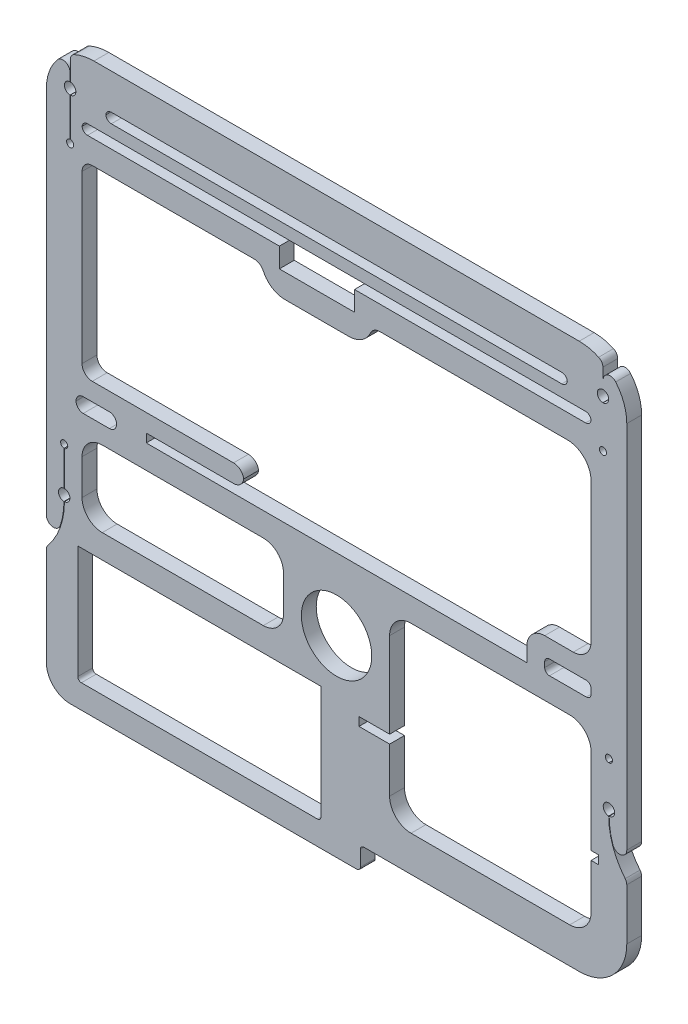
SolidWorks part; units mm, degrees
ref_plane "Front Plane" through (0, 0, 0) normal (0, 0, 1) x (1, 0, 0)
ref_plane "Top Plane" through (0, 0, 0) normal (0, 1, 0) x (1, 0, 0)
ref_plane "Right Plane" through (0, 0, 0) normal (1, 0, 0) x (0, 0, -1)
sketch "Sketch1" plane through (0, 0, 0) normal (0, 0, 1) x (1, 0, 0)
  line L0 (63.9883, 88.3985) -> (63.9883, 84.5885) construction
  line L1 (48.2422, 30.1083) -> (110.2188, 30.1083)
  line L2 (48.2422, 30.1083) -> (48.2422, 88.3985)
  line L3 (48.2422, 88.3985) -> (110.2188, 88.3985)
  line L4 (110.2188, 30.1083) -> (110.2188, 88.3985)
  line L5 (106.4088, 84.5885) -> (52.0522, 84.5885)
  line L6 (106.4088, 84.5885) -> (106.4088, 33.9183)
  line L7 (106.4088, 33.9183) -> (52.0522, 33.9183)
  line L8 (52.0522, 84.5885) -> (52.0522, 33.9183)
  line L9 (63.9883, 86.4935) -> (18.0707, 86.4935) construction
  line L10 (52.0522, 41.2855) -> (48.2422, 41.2855) construction
  line L11 (50.1472, 41.2855) -> (50.1472, 25.8577) construction
  line L12 (13.5248, 33.9183) -> (13.5248, 30.1083) construction
  line L13 (13.5248, 32.0133) -> (21.1598, 32.0133) construction
  line L14 (110.2188, 38.1916) -> (106.4088, 38.1916) construction
  line L15 (108.3138, 38.1916) -> (108.3138, 22.3321) construction
  line L16 (106.4088, 54.6152) -> (106.4088, 79.5085) construction
  line L17 (52.0522, 74.5555) -> (52.0522, 54.6152) construction
  line L22 (79.0876, 86.4935) -> (79.6338, 86.4935) construction
  line L23 (96.5564, 32.0133) -> (96.0102, 32.0133) construction
  dimension "D1" = 3.81
  dimension "D2" = 3.81
extrude "Boss-Extrude1" add sketch "Sketch1" along normal blind 1.5875
sketch "Sketch2" plane through (0, 0, 0) normal (0, 0, -1) x (-1, 0, 0)
  line L0 (-106.4088, 33.9183) -> (-106.4088, 84.5885) construction
  line L1 (-106.4088, 55.8724) -> (-52.0522, 55.8724)
  line L2 (-106.4088, 55.8724) -> (-106.4088, 53.3324)
  line L3 (-106.4088, 53.3324) -> (-52.0522, 53.3324)
  line L4 (-52.0522, 55.8724) -> (-52.0522, 53.3324)
  line L5 (-52.0522, 84.5885) -> (-52.0522, 33.9183) construction
  line L7 (-99.5505, 55.8724) -> (-58.9105, 55.8724) construction
  line L8 (-99.4108, 81.1849) -> (-61.0568, 81.1849) construction
  line L9 (-80.5132, 79.0767) -> (-73.7568, 79.0767) construction
  line L10 (-80.5132, 81.1849) -> (-80.5132, 79.0767) construction
  line L11 (-106.4088, 81.1849) -> (-81.1482, 81.1849)
  line L12 (-106.4088, 81.1849) -> (-106.4088, 78.6449)
  line L13 (-106.4088, 78.6449) -> (-83.0532, 78.6449)
  line L14 (-52.0522, 81.1849) -> (-52.0522, 78.6449)
  line L15 (-106.4088, 83.5217) -> (-52.0522, 83.5217)
  line L16 (-106.4088, 83.5217) -> (-106.4088, 82.2517)
  line L17 (-106.4088, 82.2517) -> (-52.0522, 82.2517)
  line L18 (-52.0522, 83.5217) -> (-52.0522, 82.2517)
  line L19 (-73.7568, 79.0767) -> (-73.7568, 81.1849) construction
  line L20 (-80.5132, 81.1849) -> (-80.5132, 79.0767) construction
  line L21 (-73.7568, 79.0767) -> (-73.7568, 81.1849) construction
  line L22 (-81.1482, 79.0767) -> (-81.1482, 81.1849)
  line L23 (-73.1218, 79.0767) -> (-81.1482, 79.0767)
  line L24 (-73.1218, 79.0767) -> (-73.1218, 81.1849)
  line L25 (-83.0532, 78.6449) -> (-83.0532, 76.5367)
  line L26 (-83.0532, 76.5367) -> (-71.2168, 76.5367)
  line L27 (-71.2168, 76.5367) -> (-71.2168, 78.6449)
  line L28 (-71.2168, 78.6449) -> (-52.0522, 78.6449)
  line L29 (-73.1218, 81.1849) -> (-52.0522, 81.1849)
  line L30 (-81.1482, 71.7401) -> (-80.5132, 71.7401) construction
  line L31 (-57.9086, 84.5885) -> (-57.9086, 83.5217) construction
  line L32 (-73.7568, 71.6584) -> (-73.1218, 71.6584) construction
  line L33 (-106.4088, 84.5885) -> (-52.0522, 84.5885) construction
  line L35 (-57.9086, 82.2517) -> (-57.9086, 81.1849) construction
  dimension "D1" = 2.54
  dimension "D2" = 1.905
  dimension "D3" = 2.54
  dimension "D4" = 1.905
  dimension "D5" = 1.27
  dimension "D6" = 0.635
extrude "Boss-Extrude2" add sketch "Sketch2" against normal up to surface (1.5875 mm away) up to face at (79.2305, 59.2534, 1.5875)
sketch "Sketch3" plane through (0, 0, 0) normal (0, 0, -1) x (-1, 0, 0)
  line L1 (-69.3242, 58.6918) -> (-69.3242, 56.7868)
  line L3 (-58.9105, 56.7868) -> (-99.5505, 56.7868) construction
  line L12 (-69.3242, 56.7868) -> (-52.0522, 56.7868)
  line L14 (-52.0522, 78.6449) -> (-52.0522, 55.8724) construction
  line L15 (-52.0522, 56.7868) -> (-52.0522, 58.6918)
  line L16 (-52.0522, 58.6918) -> (-69.3242, 58.6918)
  dimension "D1" = 1.905
  dimension "D2" = 17.272
extrude "Boss-Extrude3" add sketch "Sketch3" against normal up to surface (1.5875 mm away) up to face at (79.2305, 84.0551, 1.5875)
sketch "Sketch14" plane through (0, 0, 1.5875) normal (0, 0, 1) x (1, 0, 0)
  line L0 (77.0492, 42.694) -> (51.5984, 42.694) construction
  line L1 (84.8947, 41.932) -> (84.8947, 50.7924) construction
  line L2 (84.8947, 33.9183) -> (84.8947, 53.3324)
  line L4 (77.0492, 42.694) -> (52.0522, 42.694)
  line L5 (52.0522, 53.3324) -> (52.0522, 33.9183) construction
  line L6 (52.0522, 53.3324) -> (106.4088, 53.3324) construction
  line L7 (52.0522, 33.9183) -> (106.4088, 33.9183) construction
  line L9 (77.0492, 42.694) -> (77.0492, 33.9183)
  line L10 (77.0492, 33.9183) -> (84.8947, 33.9183)
  line L11 (52.0522, 53.3324) -> (84.8947, 53.3324)
  line L12 (52.0522, 53.3324) -> (52.0522, 42.694)
extrude "Boss-Extrude9" add sketch "Sketch14" against normal up to surface (1.5875 mm away) up to face at (78.1827, 80.9246, 0)
sketch "Sketch5" plane through (0, 0, 0) normal (0, 0, -1) x (-1, 0, 0)
  line L1 (-51.5984, 30.2353) -> (-77.5572, 30.2353) construction
  line L2 (-51.5984, 30.2353) -> (-51.5984, 42.694) construction
  line L6 (-51.5984, 42.694) -> (-77.5572, 42.694) construction
  line L7 (-77.5572, 30.2353) -> (-77.5572, 42.694) construction
  line L8 (-51.5984, 30.2353) -> (-77.5572, 30.2353)
  line L9 (-51.5984, 30.2353) -> (-51.5984, 42.694)
  line L10 (-51.5984, 42.694) -> (-77.5572, 42.694)
  line L11 (-77.5572, 30.2353) -> (-77.5572, 42.694)
  circle A1 centre (-79.2305, 48.2171) radius 3.7592 construction
  circle A2 centre (-79.2305, 48.2171) radius 3.7592
extrude "Cut-Extrude1" cut sketch "Sketch5" against normal up to surface (1.5875 mm away) up to face at (64.5507, 38.3062, 1.5875)
fillet "Fillet1" radius 5.08 3 edges at (110.2188, 30.1083, 0.7937) (48.2422, 88.3985, 0.7937) (110.2188, 88.3985, 0.7937)
fillet "Fillet2" radius 2.54 3 edges at (71.2168, 76.5367, 0.7937) (106.4088, 78.6449, 0.7937) (83.0532, 76.5367, 0.7937)
fillet "Fillet3" radius 1.0922 4 edges at (52.0522, 58.6918, 0.7937) (52.0522, 78.6449, 0.7937) (71.2168, 78.6449, 0.7937) (83.0532, 78.6449, 0.7937)
fillet "Fillet4" radius 0.5842 4 edges at (52.0522, 81.1849, 0.7937) (52.0522, 82.2517, 0.7938) (106.4088, 82.2517, 0.7937) (106.4088, 81.1849, 0.7937)
sketch "Sketch6" plane through (0, 0, 0) normal (0, 0, -1) x (-1, 0, 0)
  circle A0 centre (-107.6788, 84.5885) radius 0.6096 construction
  circle A1 centre (-50.7822, 84.5885) radius 0.6096 construction
  circle A2 centre (-108.3138, 46.6777) radius 0.6096 construction
  circle A3 centre (-50.1472, 46.6777) radius 0.6096 construction
  circle A4 centre (-107.6788, 84.5885) radius 0.6096
  circle A5 centre (-50.7822, 84.5885) radius 0.6096
  circle A6 centre (-108.3138, 46.6777) radius 0.6096
  circle A7 centre (-50.1472, 46.6777) radius 0.6096
extrude "Cut-Extrude2" cut sketch "Sketch6" against normal up to surface (1.5875 mm away) up to face at (75.4713, 48.2171, 1.5875)
sketch "Sketch9" plane through (0, 0, 1.5875) normal (0, 0, 1) x (1, 0, 0)
  line L4 (107.199, 41.932) -> (81.6212, 41.932)
  line L5 (81.6212, 41.932) -> (81.6212, 41.0176)
  line L6 (81.6212, 41.0176) -> (107.199, 41.0176)
  line L7 (107.199, 41.0176) -> (107.199, 41.932)
  line L8 (107.199, 41.932) -> (81.6212, 41.932)
  line L9 (81.6212, 41.932) -> (81.6212, 41.0176)
  line L10 (81.6212, 41.0176) -> (107.199, 41.0176)
  line L11 (107.199, 41.0176) -> (107.199, 41.932)
  dimension "D1" = 0
extrude "Cut-Extrude3" cut sketch "Sketch9" against normal up to surface (1.5875 mm away) up to face at (49.5376, 46.6777, 0)
sketch "Sketch11" plane through (0, 0, 1.5875) normal (0, 0, 1) x (1, 0, 0)
  line L0 (51.5984, 30.2353) -> (77.5572, 30.2353) construction
  line L1 (48.2422, 30.1083) -> (81.7705, 30.1083)
  line L2 (48.2422, 30.1083) -> (48.2422, 27.6953)
  line L3 (48.2422, 27.6953) -> (81.7705, 27.6953)
  line L4 (81.7705, 30.1083) -> (81.7705, 27.6953)
  line L5 (79.2305, 51.9763) -> (79.2305, -22.2214) construction
  circle A0 centre (79.2305, 48.2171) radius 3.7592 construction
  dimension "D1" = 2.54
  dimension "D2" = 2.54
extrude "Boss-Extrude6" add sketch "Sketch11" against normal up to surface (1.5875 mm away) up to face at (95.2379, 42.1917, 0)
fillet "Fillet7" radius 2.54 1 edges at (48.2422, 27.6953, 0.7937)
fillet "Fillet8" radius 0.381 2 edges at (81.7705, 27.6953, 0.7937) (81.7705, 30.1083, 0.7937)
sketch "Sketch12" plane through (0, 0, 1.5875) normal (0, 0, 1) x (1, 0, 0)
  line L0 (52.0522, 84.5885) -> (52.0522, 83.5217) construction
  line L1 (52.0522, 84.5885) -> (54.5922, 84.5885)
  line L2 (52.0522, 84.5885) -> (52.0522, 83.5217)
  line L3 (52.0522, 83.5217) -> (54.5922, 83.5217)
  line L4 (54.5922, 84.5885) -> (54.5922, 83.5217)
  line L5 (106.4088, 84.5885) -> (52.0522, 84.5885) construction
  line L6 (106.4088, 83.5217) -> (52.0522, 83.5217) construction
  line L8 (106.4088, 84.5885) -> (103.8688, 84.5885)
  line L9 (106.4088, 84.5885) -> (106.4088, 83.5217)
  line L10 (106.4088, 83.5217) -> (103.8688, 83.5217)
  line L11 (103.8688, 84.5885) -> (103.8688, 83.5217)
  dimension "D1" = 2.54
extrude "Boss-Extrude7" add sketch "Sketch12" against normal up to surface (1.5875 mm away) up to face at (95.2379, 42.1917, 0)
fillet "Fillet11" radius 0.5842 4 edges at (103.8688, 83.5217, 0.7937) (103.8688, 84.5885, 0.7937) (54.5922, 83.5217, 0.7937) (54.5922, 84.5885, 0.7937)
sketch "Sketch13" plane through (0, 0, 1.5875) normal (0, 0, 1) x (1, 0, 0)
  line L0 (50.7695, 86.0858) -> (50.7695, 85.198) construction
  line L1 (50.7949, 85.198) -> (50.7949, 87.2592) construction
  line L2 (50.7695, 83.9791) -> (50.7695, 79.8893) construction
  line L3 (50.7949, 79.8893) -> (50.7949, 83.9791) construction
  line L4 (107.6661, 85.198) -> (107.6661, 87.2592) construction
  line L5 (107.6915, 83.9791) -> (107.6915, 79.8893) construction
  line L6 (107.6661, 79.8893) -> (107.6661, 83.9791) construction
  line L7 (108.3265, 50.9963) -> (108.3265, 47.2872) construction
  line L8 (108.3011, 50.9963) -> (108.3011, 47.2872) construction
  line L9 (50.1345, 50.9963) -> (50.1345, 47.2872) construction
  line L10 (50.1599, 50.9963) -> (50.1599, 47.2872) construction
  line L11 (50.7695, 86.0858) -> (50.7695, 85.198)
  line L12 (50.7949, 85.198) -> (50.7949, 87.2592)
  line L13 (50.7695, 83.9791) -> (50.7695, 79.8893)
  line L14 (50.7949, 79.8893) -> (50.7949, 83.9791)
  line L15 (107.6661, 85.198) -> (107.6661, 87.2592)
  line L16 (107.6915, 83.9791) -> (107.6915, 79.8893)
  line L17 (107.6661, 79.8893) -> (107.6661, 83.9791)
  line L18 (108.3265, 50.9963) -> (108.3265, 47.2872)
  line L19 (108.3011, 50.9963) -> (108.3011, 47.2872)
  line L20 (50.1345, 50.9963) -> (50.1345, 47.2872)
  line L21 (50.1599, 50.9963) -> (50.1599, 47.2872)
  line L22 (48.2422, 83.3185) -> (48.2422, 30.2353) construction
  line L23 (110.2188, 35.1883) -> (110.2188, 83.3185) construction
  line L24 (48.2422, 43.8754) -> (48.2422, 40.6699)
  line L25 (110.2188, 40.6699) -> (110.2188, 43.8754)
  line L26 (107.6915, 83.9791) -> (107.6915, 79.8893)
  line L27 (107.6915, 86.0858) -> (107.6915, 85.198) construction
  line L28 (107.6915, 86.0858) -> (107.6915, 85.198)
  arc A0 (107.6661, 83.9791) -> (107.6915, 83.9791) centre (107.6788, 84.5885) ccw
  arc A1 (50.7695, 86.0858) -> (49.4225, 86.5742) centre (50.0075, 86.0858) ccw construction
  arc A2 (51.2454, 87.9546) -> (50.7949, 87.2592) centre (51.5569, 87.2592) ccw construction
  arc A3 (50.7695, 79.8893) -> (50.7949, 79.8893) centre (50.7822, 79.5085) ccw construction
  arc A4 (107.6661, 87.2592) -> (107.2156, 87.9546) centre (106.9041, 87.2592) ccw construction
  arc A5 (109.0384, 86.5742) -> (107.6915, 86.0858) centre (108.4535, 86.0858) ccw construction
  arc A6 (107.6661, 79.8893) -> (107.6915, 79.8893) centre (107.6788, 79.5085) ccw construction
  arc A7 (108.3265, 50.9963) -> (108.3011, 50.9963) centre (108.3138, 51.3771) ccw construction
  arc A8 (108.3392, 46.0687) -> (108.7338, 43.6346) centre (116.0396, 46.0681) ccw construction
  arc A9 (108.7338, 43.6346) -> (110.2188, 43.8754) centre (109.4568, 43.8754) ccw construction
  arc A10 (108.2884, 46.0687) -> (110.046, 41.153) centre (116.0396, 46.0681) ccw construction
  arc A11 (110.2188, 40.6699) -> (110.046, 41.153) centre (109.4568, 40.6699) ccw construction
  arc A12 (48.2422, 43.8754) -> (49.7271, 43.6346) centre (49.0042, 43.8754) ccw construction
  arc A13 (50.1599, 50.9963) -> (50.1345, 50.9963) centre (50.1472, 51.3771) ccw construction
  arc A14 (48.415, 41.153) -> (50.1726, 46.0687) centre (42.4214, 46.0681) ccw construction
  arc A15 (49.7271, 43.6346) -> (50.1218, 46.0687) centre (42.4214, 46.0681) ccw construction
  arc A16 (48.415, 41.153) -> (48.2422, 40.6699) centre (49.0042, 40.6699) ccw construction
  arc A17 (50.7695, 83.9791) -> (50.7949, 83.9791) centre (50.7822, 84.5885) ccw
  arc A18 (50.7695, 86.0858) -> (49.4225, 86.5742) centre (50.0075, 86.0858) ccw
  arc A19 (51.2454, 87.9546) -> (50.7949, 87.2592) centre (51.5569, 87.2592) ccw
  arc A20 (50.7695, 79.8893) -> (50.7949, 79.8893) centre (50.7822, 79.5085) ccw
  arc A21 (107.6661, 87.2592) -> (107.2156, 87.9546) centre (106.9041, 87.2592) ccw
  arc A22 (109.0384, 86.5742) -> (107.6915, 86.0858) centre (108.4535, 86.0858) ccw
  arc A23 (107.6661, 79.8893) -> (107.6915, 79.8893) centre (107.6788, 79.5085) ccw
  arc A24 (108.3265, 50.9963) -> (108.3011, 50.9963) centre (108.3138, 51.3771) ccw
  arc A25 (108.3392, 46.0687) -> (108.7338, 43.6346) centre (116.0396, 46.0681) ccw
  arc A26 (108.7338, 43.6346) -> (110.2188, 43.8754) centre (109.4568, 43.8754) ccw
  arc A27 (108.2884, 46.0687) -> (110.046, 41.153) centre (116.0396, 46.0681) ccw
  arc A28 (110.2188, 40.6699) -> (110.046, 41.153) centre (109.4568, 40.6699) ccw
  arc A29 (48.2422, 43.8754) -> (49.7271, 43.6346) centre (49.0042, 43.8754) ccw
  arc A30 (50.1599, 50.9963) -> (50.1345, 50.9963) centre (50.1472, 51.3771) ccw
  arc A31 (48.415, 41.153) -> (50.1726, 46.0687) centre (42.4214, 46.0681) ccw
  arc A32 (49.7271, 43.6346) -> (50.1218, 46.0687) centre (42.4214, 46.0681) ccw
  arc A33 (48.415, 41.153) -> (48.2422, 40.6699) centre (49.0042, 40.6699) ccw
  circle A34 centre (50.7822, 84.5885) radius 0.6096 construction
  circle A35 centre (107.6788, 84.5885) radius 0.6096 construction
  circle A36 centre (108.3138, 46.6777) radius 0.6096 construction
  circle A37 centre (50.1472, 46.6777) radius 0.6096 construction
  arc A38 (53.3222, 88.3985) -> (48.2422, 83.3185) centre (53.3222, 83.3185) ccw construction
  arc A39 (110.2188, 83.3185) -> (105.1388, 88.3985) centre (105.1388, 83.3185) ccw construction
  arc A40 (50.7949, 85.198) -> (50.7695, 85.198) centre (50.7822, 84.5885) ccw
  arc A41 (107.6661, 83.9791) -> (107.6915, 83.9791) centre (107.6788, 84.5885) ccw
  arc A42 (108.3265, 47.2872) -> (108.3011, 47.2872) centre (108.3138, 46.6777) ccw
  arc A43 (50.1218, 46.0687) -> (50.1726, 46.0687) centre (50.1472, 46.6777) ccw
  arc A44 (51.2454, 87.9546) -> (49.4225, 86.5742) centre (53.3222, 83.3185) ccw
  arc A45 (109.0384, 86.5742) -> (107.2156, 87.9546) centre (105.1388, 83.3185) ccw
  arc A46 (50.1599, 47.2872) -> (50.1345, 47.2872) centre (50.1472, 46.6777) ccw
  arc A47 (108.2884, 46.0687) -> (108.3392, 46.0687) centre (108.3138, 46.6777) ccw
  arc A48 (107.6915, 85.198) -> (107.6661, 85.198) centre (107.6788, 84.5885) ccw
extrude "Cut-Extrude4" cut sketch "Sketch13" against normal through all contours A48 L28 A22 A45 A21 L15 | L17 A23 L16 A0 | A47 A27 A28 L25 A26 A25 | A42 L18 A24 L19 | A43 A32 A29 L24 A33 A31 | A46 L21 A30 L20 | A19 A44 A18 L11 A40 L12 | L13 A20 L14 A17
fillet "Fillet12" radius 2.286 4 edges at (106.4088, 33.9183, 0.7937) (106.4088, 53.3324, 0.7937) (84.8947, 33.9183, 0.7937) (84.8947, 53.3324, 0.7937)
fillet "Fillet13" radius 0.381 2 edges at (51.5984, 30.2353, 0.7937) (77.5572, 30.2353, 0.7937)
sketch "Sketch15" plane through (0, 0, 1.5875) normal (0, 0, 1) x (1, 0, 0)
  line L0 (73.5663, 51.1734) -> (73.5663, 47.393) construction
  line L1 (71.4073, 45.234) -> (54.2112, 45.234) construction
  line L2 (52.0522, 51.1734) -> (52.0522, 47.393) construction
  line L3 (54.2112, 53.3324) -> (71.4073, 53.3324) construction
  line L4 (73.5663, 51.1734) -> (73.5663, 47.393)
  line L5 (71.4073, 45.234) -> (54.2112, 45.234)
  line L6 (52.0522, 51.1734) -> (52.0522, 47.393)
  line L7 (54.2112, 53.3324) -> (71.4073, 53.3324)
  arc A0 (73.5663, 51.1734) -> (71.4073, 53.3324) centre (71.4073, 51.1734) ccw construction
  arc A1 (71.4073, 45.234) -> (73.5663, 47.393) centre (71.4073, 47.393) ccw construction
  arc A2 (52.0522, 47.393) -> (54.2112, 45.234) centre (54.2112, 47.393) ccw construction
  arc A3 (54.2112, 53.3324) -> (52.0522, 51.1734) centre (54.2112, 51.1734) ccw construction
  arc A4 (73.5663, 51.1734) -> (71.4073, 53.3324) centre (71.4073, 51.1734) ccw
  arc A5 (71.4073, 45.234) -> (73.5663, 47.393) centre (71.4073, 47.393) ccw
  arc A6 (52.0522, 47.393) -> (54.2112, 45.234) centre (54.2112, 47.393) ccw
  arc A7 (54.2112, 53.3324) -> (52.0522, 51.1734) centre (54.2112, 51.1734) ccw
extrude "Cut-Extrude5" cut sketch "Sketch15" against normal through all
sketch "Sketch18" plane through (0, 0, 0) normal (0, 0, -1) x (-1, 0, 0)
  line L0 (-99.5505, 55.8724) -> (-99.5505, 59.3268)
  line L1 (-99.5505, 59.3268) -> (-106.4088, 59.3268)
  line L2 (-106.4088, 55.8724) -> (-106.4088, 76.1049) construction
  line L3 (-101.4555, 55.8724) -> (-101.4555, 57.4218)
  line L4 (-52.0522, 55.8724) -> (-106.4088, 55.8724) construction
  line L5 (-101.4555, 57.4218) -> (-106.4088, 57.4218)
  line L6 (-106.4088, 57.4218) -> (-106.4088, 59.3268)
  line L7 (-99.5505, 56.7868) -> (-58.9105, 56.7868) construction
  line L8 (-99.5505, 56.7868) -> (-99.5505, 55.8724) construction
  line L9 (-101.4555, 55.8724) -> (-99.5505, 55.8724)
  line L18 (-69.3242, 58.6918) -> (-53.1444, 58.6918)
  line L19 (-52.0522, 56.7868) -> (-69.3242, 56.7868)
  line L20 (-52.0522, 55.8724) -> (-52.0522, 56.7868)
  line L21 (-106.4088, 55.8724) -> (-52.0522, 55.8724)
  line L24 (-69.3242, 58.6918) -> (-53.1444, 58.6918)
  line L25 (-73.7198, 76.5367) -> (-80.5502, 76.5367)
  line L26 (-106.4088, 76.1049) -> (-106.4088, 55.8724)
  line L27 (-83.8472, 78.6449) -> (-103.8688, 78.6449)
  line L28 (-73.7198, 76.5367) -> (-80.5502, 76.5367)
  line L29 (-53.1444, 78.6449) -> (-70.4228, 78.6449)
  line L30 (-53.1444, 78.6449) -> (-70.4228, 78.6449)
  line L31 (-52.0522, 59.784) -> (-52.0522, 77.5527)
  line L32 (-52.0522, 59.784) -> (-52.0522, 77.5527)
  line L33 (-69.3242, 56.7868) -> (-69.3242, 58.6918)
  line L34 (-69.3242, 56.7868) -> (-69.3242, 58.6918)
  arc A6 (-82.8558, 78.011) -> (-83.8472, 78.6449) centre (-83.8472, 77.5527) ccw
  arc A8 (-82.8558, 78.011) -> (-83.8472, 78.6449) centre (-83.8472, 77.5527) ccw
  arc A9 (-82.8558, 78.011) -> (-80.5502, 76.5367) centre (-80.5502, 79.0767) ccw
  arc A10 (-82.8558, 78.011) -> (-80.5502, 76.5367) centre (-80.5502, 79.0767) ccw
  arc A11 (-73.7198, 76.5367) -> (-71.4142, 78.011) centre (-73.7198, 79.0767) ccw
  arc A12 (-103.8688, 78.6449) -> (-106.4088, 76.1049) centre (-103.8688, 76.1049) ccw
  arc A13 (-73.7198, 76.5367) -> (-71.4142, 78.011) centre (-73.7198, 79.0767) ccw
  arc A14 (-70.4228, 78.6449) -> (-71.4142, 78.011) centre (-70.4228, 77.5527) ccw
  arc A15 (-70.4228, 78.6449) -> (-71.4142, 78.011) centre (-70.4228, 77.5527) ccw
  arc A16 (-52.0522, 77.5527) -> (-53.1444, 78.6449) centre (-53.1444, 77.5527) ccw
  arc A17 (-52.0522, 77.5527) -> (-53.1444, 78.6449) centre (-53.1444, 77.5527) ccw
  arc A18 (-53.1444, 58.6918) -> (-52.0522, 59.784) centre (-53.1444, 59.784) ccw
  arc A19 (-53.1444, 58.6918) -> (-52.0522, 59.784) centre (-53.1444, 59.784) ccw
  dimension "D1" = 1.905
  dimension "D2" = 1.905
  dimension "D3" = 2.54
  dimension "D4" = 0
extrude "Boss-Extrude11" add sketch "Sketch18" against normal up to surface (1.5875 mm away) up to face at (62.8092, 49.2832, 1.5875)
fillet "Fillet15" radius 0.508 4 edges at (106.4088, 55.8724, 0.7937) (106.4088, 57.4218, 0.7937) (101.4555, 57.4218, 0.7938) (101.4555, 55.8724, 0.7938)
sketch "Sketch19" plane through (0, 0, 0) normal (0, 0, -1) x (-1, 0, 0)
  line L0 (-58.9105, 56.7868) -> (-58.9105, 55.8724) construction
  line L1 (-58.9105, 56.7868) -> (-58.9105, 55.8724)
  line L2 (-52.0522, 55.8724) -> (-99.5505, 55.8724) construction
  line L3 (-52.0522, 56.7868) -> (-52.0522, 55.8724) construction
  line L4 (-69.3242, 56.7868) -> (-52.0522, 56.7868) construction
  line L5 (-52.0522, 55.8724) -> (-58.9105, 55.8724)
  line L6 (-52.0522, 56.7868) -> (-52.0522, 55.8724)
  line L7 (-58.9105, 56.7868) -> (-52.0522, 56.7868)
extrude "Boss-Extrude12" add sketch "Sketch19" against normal up to surface (1.5875 mm away) up to face at (103.9321, 56.6471, 1.5875)
sketch "Sketch20" plane through (0, 0, 0) normal (0, 0, -1) x (-1, 0, 0)
  line L0 (-58.9105, 56.3296) -> (-55.7355, 56.3296) construction
  line L1 (-55.7355, 56.7868) -> (-51.4172, 56.7868)
  line L2 (-55.7355, 56.7868) -> (-55.7355, 55.2374)
  line L3 (-55.7355, 55.2374) -> (-51.4172, 55.2374)
  line L4 (-51.4172, 56.7868) -> (-51.4172, 55.2374)
  line L5 (-58.9105, 56.7868) -> (-58.9105, 55.8724) construction
  line L6 (-48.2422, 83.3185) -> (-48.2422, 43.8754) construction
  line L7 (-51.4172, 56.3296) -> (-48.2422, 56.3296) construction
  line L8 (-54.9256, 56.7868) -> (-54.9256, 58.6918) construction
  line L10 (-53.1444, 58.6918) -> (-69.3242, 58.6918) construction
  line L11 (-54.6333, 55.2374) -> (-54.6333, 53.3324) construction
  line L12 (-71.4073, 53.3324) -> (-54.2112, 53.3324) construction
  point P8 (-55.7355, 56.0121)
  dimension "D1" = 3.175
  dimension "D2" = 1.905
extrude "Cut-Extrude7" cut sketch "Sketch20" against normal through all
fillet "Fillet16" radius 0.762 4 edges at (55.7355, 55.2374, 0.7938) (51.4172, 56.7868, 0.7938) (51.4172, 55.2374, 0.7937) (55.7355, 56.7868, 0.7938)
fillet "Fillet17" radius 1.905 2 edges at (99.5505, 59.3268, 0.7938) (106.4088, 59.3268, 0.7938)
fillet "Fillet18" radius 1.0922 2 edges at (69.3242, 56.7868, 0.7937) (69.3242, 58.6918, 0.7937)
